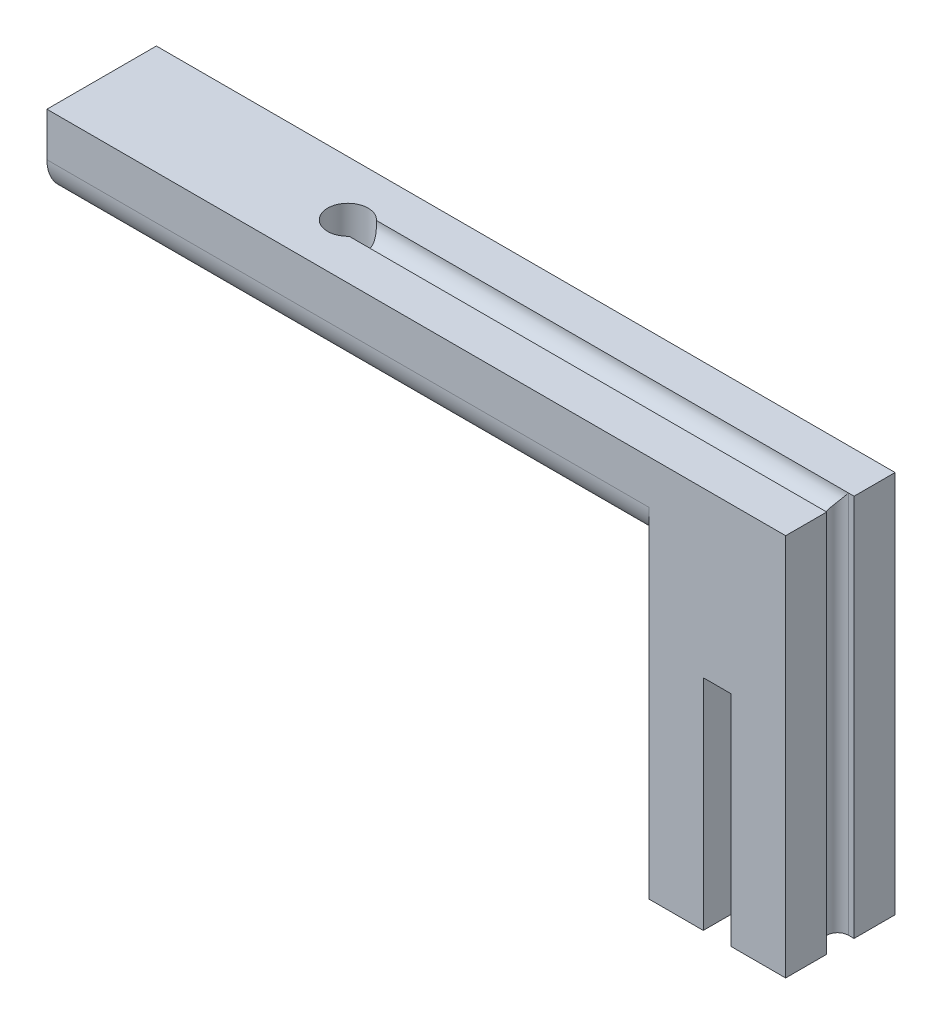
SolidWorks part; units mm, degrees
ref_plane "Front Plane" through (0, 0, 0) normal (0, 0, 1) x (1, 0, 0)
ref_plane "Top Plane" through (0, 0, 0) normal (0, 1, 0) x (1, 0, 0)
ref_plane "Right Plane" through (0, 0, 0) normal (1, 0, 0) x (0, 0, -1)
sketch "Sketch1" plane through (0, 0, 0) normal (0, 0, 1) x (1, 0, 0)
  line L0 (0, 0) -> (0, 70)
  line L1 (0, 70) -> (-135, 70)
  line L2 (-135, 70) -> (-135, 55)
  line L3 (-135, 55) -> (-25, 55)
  line L4 (-25, 55) -> (-25, 0)
  line L5 (-25, 0) -> (0, 0)
  point P7 (-105, 42.1263)
  dimension "D1" = 25
  dimension "D2" = 70
  dimension "D3" = 15
  dimension "D4" = 110
extrude "Boss-Extrude1" add sketch "Sketch1" along normal blind 20
sketch "Sketch2" plane through (0, 0, 20) normal (0, 0, 1) x (1, 0, 0)
  line L0 (-25, 0) -> (0, 0) construction
  line L1 (-15.05, 0) -> (-9.95, 0)
  line L2 (-15.05, 0) -> (-15.05, 40)
  line L3 (-15.05, 40) -> (-9.95, 40)
  line L4 (-9.95, 0) -> (-9.95, 40)
  line L5 (-25, 0) -> (-15.05, 0) construction
  line L6 (-9.95, 0) -> (0, 0) construction
  dimension "D1" = 5.1
  dimension "D2" = 40
extrude "Cut-Extrude1" cut sketch "Sketch2" against normal up to surface (20 mm away) up to face at (-53.3333, 41.6667, 0)
fillet "Fillet1" radius 7 2 edges at (-80, 55, 0) (-80, 55, 20)
sketch "Sketch5" plane through (0, 70, 0) normal (0, 1, 0) x (1, 0, 0)
  line L0 (-135, -10) -> (-90, -10) construction
  line L1 (-135, -20) -> (-135, 0) construction
  circle A0 centre (-90, -10) radius 3.7
  dimension "D2" = 7.4
  dimension "D1" = 45
extrude "Cut-Extrude3" cut sketch "Sketch5" against normal up to surface (15 mm away) up to face at (-80, 55, 10)
sketch "Sketch6" plane through (0, 70, 0) normal (0, 1, 0) x (1, 0, 0)
  line L0 (0, -20) -> (0, 0) construction
  line L1 (-87.2724, -7.5) -> (0, -7.5)
  line L2 (-87.2724, -7.5) -> (-87.2724, -12.5)
  line L3 (-87.2724, -12.5) -> (0, -12.5)
  line L4 (0, -7.5) -> (0, -12.5)
  line L5 (-87.2724, -10) -> (-86.3, -10) construction
  circle A0 centre (-90, -10) radius 3.7 construction
  point P10 (0, 0)
  dimension "D1" = 5
extrude "Cut-Extrude4" cut sketch "Sketch6" against normal blind 3
fillet "Fillet2" radius 3 2 edges at (-43.6362, 67, 12.5) (-43.6362, 67, 7.5)
sketch "Sketch7" plane through (0, 70, 0) normal (0, 1, 0) x (1, 0, 0)
  line L0 (-87.2724, -12.5) -> (0, -12.5) construction
  line L1 (0, -7.5) -> (-3, -7.5)
  line L2 (0, -7.5) -> (0, -12.5)
  line L3 (0, -12.5) -> (-3, -12.5)
  line L4 (-3, -7.5) -> (-3, -12.5)
  dimension "D1" = 3
extrude "Cut-Extrude5" cut sketch "Sketch7" against normal up to surface (70 mm away) up to face at (-4.975, 0, 10)
fillet "Fillet3" radius 2 2 edges at (-3, 35, 12.5) (-3, 35, 7.5)
